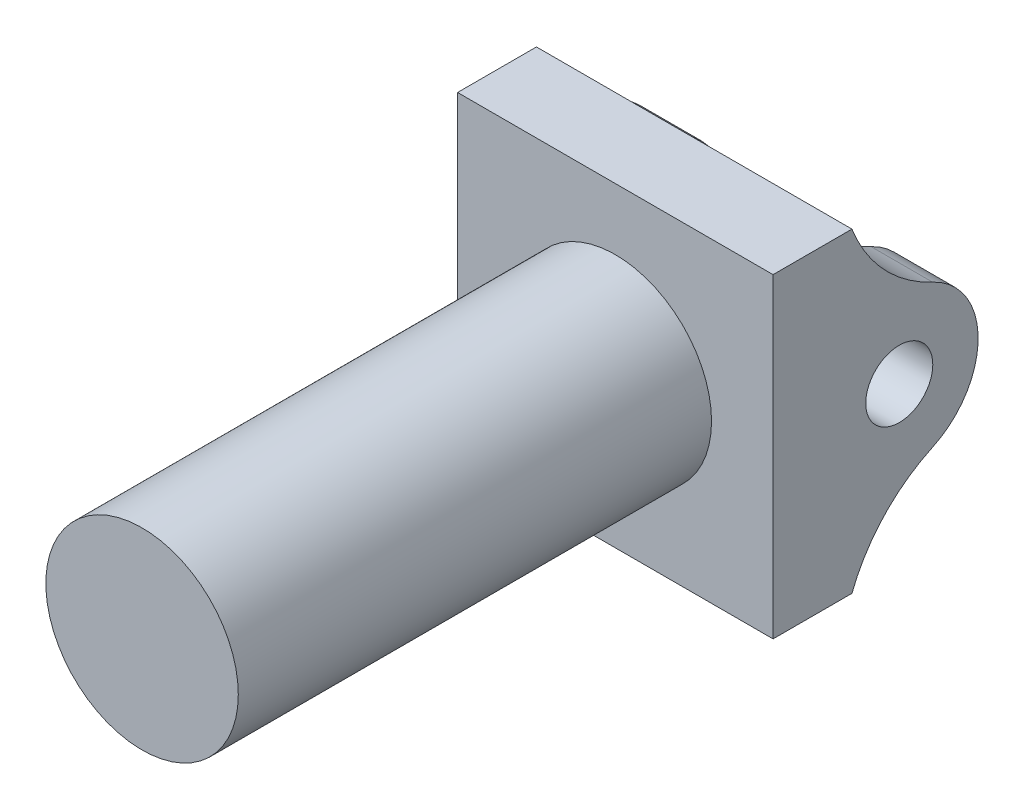
SolidWorks part; units mm, degrees
ref_plane "Front Plane" through (0, 0, 0) normal (0, 0, 1) x (1, 0, 0)
ref_plane "Top Plane" through (0, 0, 0) normal (0, 1, 0) x (1, 0, 0)
ref_plane "Right Plane" through (0, 0, 0) normal (1, 0, 0) x (0, 0, -1)
sketch "Sketch2" plane through (0, 0, 0) normal (0, 0, 1) x (1, 0, 0)
  circle A0 centre (0, 0) radius 6.1
  dimension "D1" = 12.2
extrude "Boss-Extrude1" add sketch "Sketch2" along normal blind 30
sketch "Sketch3" plane through (0, 0, 0) normal (0, 0, -1) x (-1, 0, 0)
  line L1 (-10, -10) -> (10, -10)
  line L2 (-10, -10) -> (-10, 10)
  line L3 (-10, 10) -> (10, 10)
  line L4 (10, -10) -> (10, 10)
  line L5 (-10, -10) -> (10, 10) construction
  line L6 (-10, 10) -> (10, -10) construction
  point P0 (0, 0)
  dimension "D1" = 20
  dimension "D2" = 20
extrude "Boss-Extrude2" add sketch "Sketch3" along normal blind 5
sketch "Sketch4" plane through (10, 0, 0) normal (1, 0, 0) x (0, 0, -1)
  line L0 (5, 0) -> (5, 5)
  line L1 (5, 10) -> (5, -10) construction
  line L2 (5, 5) -> (8, 5)
  line L5 (8, -5) -> (5, -5)
  line L6 (5, -5) -> (5, 0)
  arc A0 (8, -5) -> (8, 5) centre (8, 0) ccw
  circle A1 centre (8, 0) radius 2.125
  dimension "D2" = 4.25
  dimension "D1" = 3
  dimension "D3" = 10
  dimension "D4" = 5
extrude "Boss-Extrude3" add sketch "Sketch4" against normal blind 20
sketch "Sketch5" plane through (0, 0, 0) normal (0, 1, 0) x (1, 0, 0)
  line L0 (10, 13) -> (-10, 13) construction
  line L1 (-6.1, 21) -> (6.1, 21)
  line L2 (-6.1, 21) -> (-6.1, 5)
  line L3 (-6.1, 5) -> (6.1, 5)
  line L4 (6.1, 21) -> (6.1, 5)
  line L5 (-6.1, 21) -> (6.1, 5) construction
  line L6 (-6.1, 5) -> (6.1, 21) construction
  line L7 (-10, 5) -> (10, 5) construction
  point P0 (0, 13)
  dimension "D1" = 12.2
extrude "Cut-Extrude1" cut sketch "Sketch5" against normal blind 20 and the other way blind 20
fillet "Fillet2" radius 10 4 edges at (-8.05, 5, -5) (8.05, 5, -5) (-8.05, -5, -5) (8.05, -5, -5)
